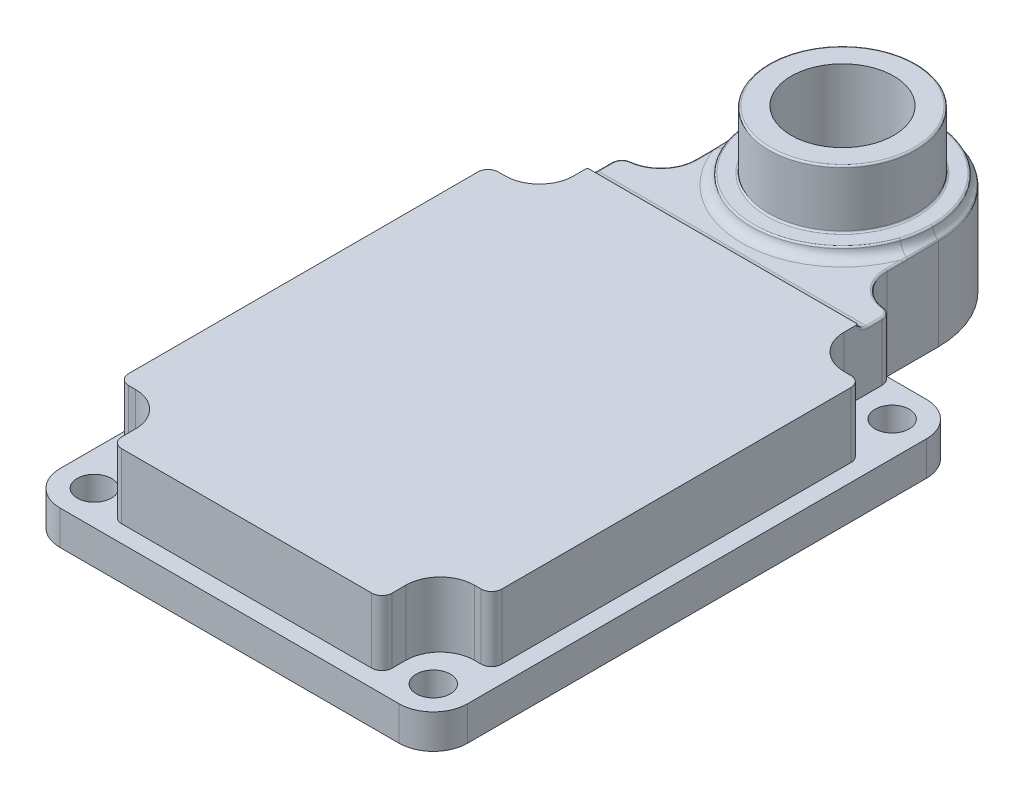
SolidWorks part; units mm, degrees
ref_plane "前视基准面" through (0, 0, 0) normal (0, 0, 1) x (1, 0, 0)
ref_plane "上视基准面" through (0, 0, 0) normal (0, 1, 0) x (1, 0, 0)
ref_plane "右视基准面" through (0, 0, 0) normal (1, 0, 0) x (0, 0, -1)
sketch "草图1" plane through (0, 0, 0) normal (0, 1, 0) x (1, 0, 0)
  line L1 (0, 0) -> (119, 0)
  line L2 (0, 0) -> (0, -154)
  line L3 (0, -154) -> (119, -154)
  line L4 (119, 0) -> (119, -154)
  dimension "D1" = 154
  dimension "D2" = 119
extrude "拉伸1" add sketch "草图1" along normal blind 10
sketch "草图2" plane through (0, 10, 0) normal (0, 1, 0) x (1, 0, 0)
  line L0 (59.5, 0) -> (59.5, 53) construction
  line L1 (119, 0) -> (0, 0) construction
  line L2 (31.5, 25) -> (31.5, 0)
  line L3 (31.5, 0) -> (87.5, 0)
  line L4 (87.5, 0) -> (87.5, 25)
  arc A0 (31.5, 25) -> (87.5, 25) centre (59.5, 25) cw
  dimension "D1" = 53
extrude "拉伸2" add sketch "草图2" against normal up to vertex (10 mm away) up to point (119, 0, 0)
sketch "草图3" plane through (0, 10, 0) normal (0, 1, 0) x (1, 0, 0)
  line L0 (0, 0) -> (0, -154) construction
  line L1 (5, -149) -> (114, -149)
  line L2 (5, -149) -> (5, -5.402)
  line L4 (114, -149) -> (114, -5.402)
  line L5 (0, -154) -> (119, -154) construction
  line L6 (119, -154) -> (119, 0) construction
  line L7 (31.5, 25) -> (31.5, 0)
  line L8 (31.5, 0) -> (5, 0)
  line L9 (31.5, 0) -> (0, 0) construction
  line L10 (5, 0) -> (5, -5.402)
  line L11 (87.5, 25) -> (87.5, 0)
  line L12 (87.5, 0) -> (114, 0)
  line L13 (119, 0) -> (87.5, 0) construction
  line L14 (114, 0) -> (114, -5.402)
  arc A0 (31.5, 25) -> (87.5, 25) centre (59.5, 25) cw
  arc A1 (87.5, 25) -> (31.5, 25) centre (59.5, 25) ccw construction
  dimension "D1" = 5
  dimension "D2" = 5
  dimension "D3" = 5
extrude "拉伸3" add sketch "草图3" along normal blind 19
sketch "草图4" plane through (0, 29, 0) normal (0, 1, 0) x (1, 0, 0)
  line L0 (59.5, -154) -> (59.5, 16.0555) construction
  line L1 (114, -149) -> (99, -149)
  line L2 (114, -149) -> (114, -132)
  line L3 (114, -132) -> (99, -132)
  line L4 (99, -149) -> (99, -132)
  line L5 (114, 0) -> (99, 0)
  line L6 (114, 0) -> (114, -24)
  line L7 (114, -24) -> (99, -24)
  line L8 (99, 0) -> (99, -24)
  line L9 (0, -154) -> (119, -154) construction
  line L10 (20, 0) -> (20, -24)
  line L11 (5, -24) -> (20, -24)
  line L12 (5, 0) -> (5, -24)
  line L13 (5, 0) -> (20, 0)
  line L14 (20, -149) -> (20, -132)
  line L15 (5, -132) -> (20, -132)
  line L16 (5, -149) -> (5, -132)
  line L17 (5, -149) -> (20, -149)
  dimension "D1" = 108
  dimension "D2" = 17
  dimension "D3" = 15
  dimension "D4" = 15
extrude "切除-拉伸1" cut sketch "草图4" against normal up to vertex (19 mm away) up to point (119, 10, 0)
fillet "圆角1" radius 10 4 edges at (99, 19.5, 132) (99, 19.5, 24) (20, 19.5, 24) (20, 19.5, 132)
fillet "圆角2" radius 10 4 edges at (119, 5, 0) (0, 5, 0) (0, 5, 154) (119, 5, 154)
fillet "圆角3" radius 10 2 edges
fillet "圆角4" radius 3 8 edges at (99, 19.5, 0) (114, 19.5, 24) (99, 19.5, 149) (114, 19.5, 132) (20, 19.5, 149) (5, 19.5, 132) (5, 19.5, 24) (20, 19.5, 0)
sketch "草图5" plane through (0, 10, 0) normal (0, 1, 0) x (1, 0, 0)
  circle A0 centre (109, -10) radius 5
  circle A1 centre (10, -10) radius 5
  circle A2 centre (10, -144) radius 5
  circle A3 centre (109, -144) radius 5
  dimension "D1" = 10
  dimension "D2" = 10
  dimension "D3" = 10
  dimension "D4" = 10
extrude "切除-拉伸2" cut sketch "草图5" against normal through all
sketch "草图7" plane through (0, 29, 0) normal (0, 1, 0) x (1, 0, 0)
  line L0 (109, 0) -> (97.5, 0) construction
  line L1 (11.4055, 57.5838) -> (104.0856, 57.5838)
  line L2 (11.4055, 57.5838) -> (11.4055, -10)
  line L3 (11.4055, -10) -> (104.0856, -10)
  line L4 (104.0856, 57.5838) -> (104.0856, -10)
  dimension "D1" = 10
extrude "切除-拉伸3" cut sketch "草图7" against normal blind 2
fillet "圆角5" radius 3 1 edges at (59.5, 27, 10)
sketch "草图8" plane through (0, 27, 0) normal (0, 1, 0) x (1, 0, 0)
  circle A0 centre (59.5, 25) radius 26.4436
extrude "拉伸4" add sketch "草图8" along normal blind 3
fillet "圆角6" radius 3 1 edges at (59.5, 27, 1.4436)
sketch "草图9" plane through (0, 30, 0) normal (0, 1, 0) x (1, 0, 0)
  circle A0 centre (59.5, 25) radius 21.5
  dimension "D1" = 43
extrude "拉伸5" add sketch "草图9" along normal blind 17
sketch "草图10" plane through (0, 47, 0) normal (0, 1, 0) x (1, 0, 0)
  circle A0 centre (59.5, 25) radius 15
  dimension "D1" = 30
extrude "切除-拉伸4" cut sketch "草图10" against normal through all
fillet "圆角7" radius 0.5 4 edges at (59.5, 30, -51.4436) (59.5, 30, 1.4436) (59.5, 30, -3.5) (59.5, 47, -3.5)
fillet "圆角8" radius 0.5 13 edges at (20, 27.5505, 8.9036) (20.7596, 27, 0.918) (20, 27, 5.0424) (28.9679, 27, -3.3494) (31.5, 27, -12.9469) (31.5, 27, -20.4469) (59.5, 27, -53) (87.5, 27, -20.4469) (87.5, 27, -12.9469) (90.0321, 27, -3.3494) (98.2404, 27, 0.918) (99, 27, 5.0424) (99, 27.5505, 8.9036)
